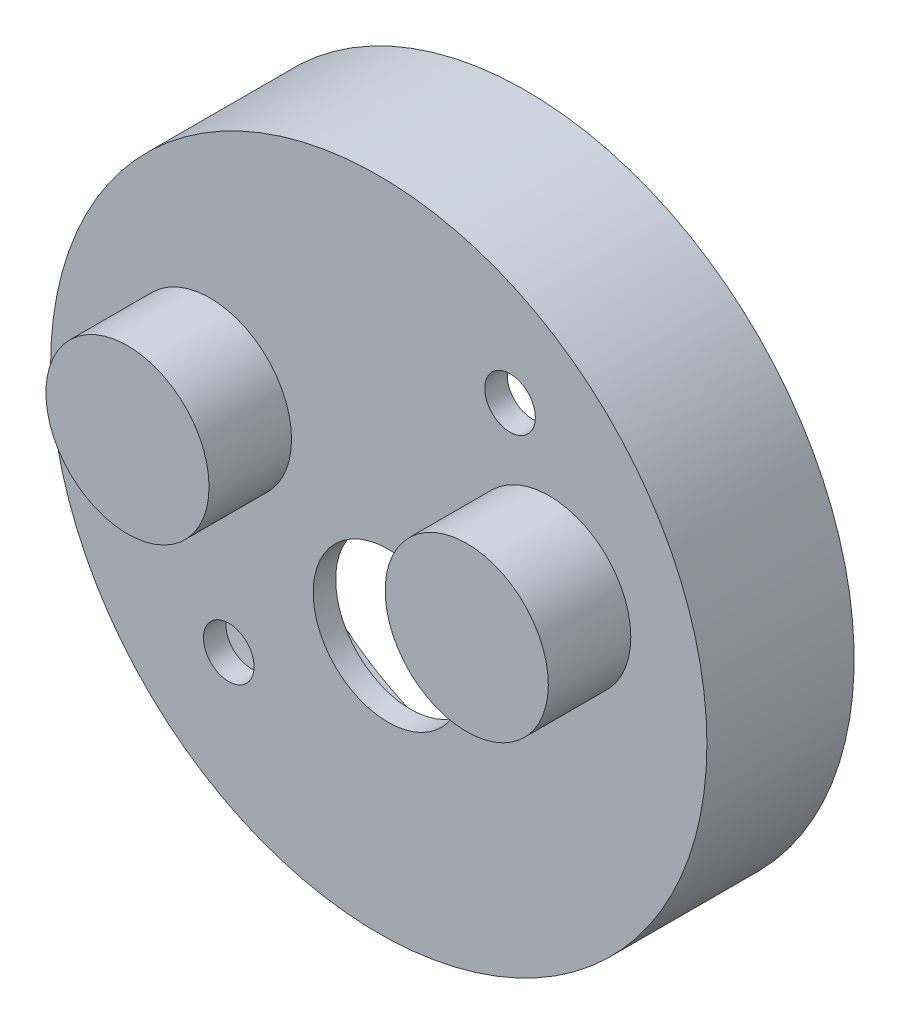
SolidWorks part; units mm, degrees
note: '?' marks a value the reader was unsure of.
ref_plane "Top Plane" through (0, 0, 0) normal (0, 0, 1) x (1, 0, 0)
ref_plane "Right Plane" through (0, 0, 0) normal (0, 1, 0) x (1, 0, 0)
ref_plane "Front Plane" through (0, 0, 0) normal (1, 0, 0) x (0, 0, -1)
ref_axis "x-axis" through (-88.99, 0, 0) along (1, 0, 0)?
ref_axis "y-axis" through (0, -55, 0) along (0, 1, 0)?
ref_axis "z-axis" through (0, 0, 55) along (0, 0, -1)?
sketch "Sketch5" plane through (0, 0, 0) normal (0, 0, 1) x (1, 0, 0)
  circle A2 centre (70.0005, -49.4998) radius 17.5
  dimension "D1" = 35
extrude "Boss-Extrude1" add sketch "Sketch5" along normal blind 5.85
sketch "Sketch8" plane through (0, 0, 0) normal (0, 0, 1) x (1, 0, 0)
  circle A0 centre (79.0908, -46.5908) radius 4.35
  circle A1 centre (61, -46.5) radius 4.35
  dimension "D1" = 8.7
extrude "Boss-Extrude2" add sketch "Sketch8" along normal blind 10.25
sketch "Sketch13" plane through (0, 0, 0) normal (0, 0, 1) x (1, 0, 0)
  line L0 (70, -33.4998) -> (70, -31.9998) construction
  line L5 (66, -39.4998) -> (63, -39.4998) construction
  line L6 (77, -39) -> (74, -39) construction
  circle A0 centre (70.5, -53) radius 4
  circle A3 centre (77, -39) radius 1.35
  circle A5 centre (62, -58.017) radius 1.35
  circle A6 centre (79.0908, -46.5908) radius 3.65
  circle A7 centre (61, -46.5) radius 3.65
  circle A15 centre (70.0005, -49.4998) radius 17.5 construction
  dimension "D1" = 2.7
  dimension "D3" = 1.5
extrude "Cut-Extrude1" cut sketch "Sketch13" along normal blind 9.55
sketch "Sketch14" plane through (0, 0, 0) normal (0, 0, 1) x (1, 0, 0)
  circle A0 centre (70.0005, -49.4998) radius 15.5
extrude "Cut-Extrude2" cut sketch "Sketch14" along normal blind 4.65
sketch "Sketch15" plane through (0, 0, 0) normal (0, 0, -1) x (1, 0, 0)
  circle A0 centre (70.0005, 49.4998) radius 17.5 construction
  arc A1 (74, 34.5247) -> (66, 34.525) centre (70.0005, 49.4998) ccw construction
  circle A2 centre (70.0005, 49.4998) radius 17.5
  arc A3 (74, 34.5247) -> (66, 34.525) centre (70.0005, 49.4998) ccw
  arc A4 (74, 34.5247) -> (66, 34.525) centre (70.0005, 49.4998) ccw construction
  arc A5 (74, 34.5247) -> (66, 34.525) centre (70.0005, 49.4998) ccw
extrude "Boss-Extrude3" add sketch "Sketch15" along normal blind 2
